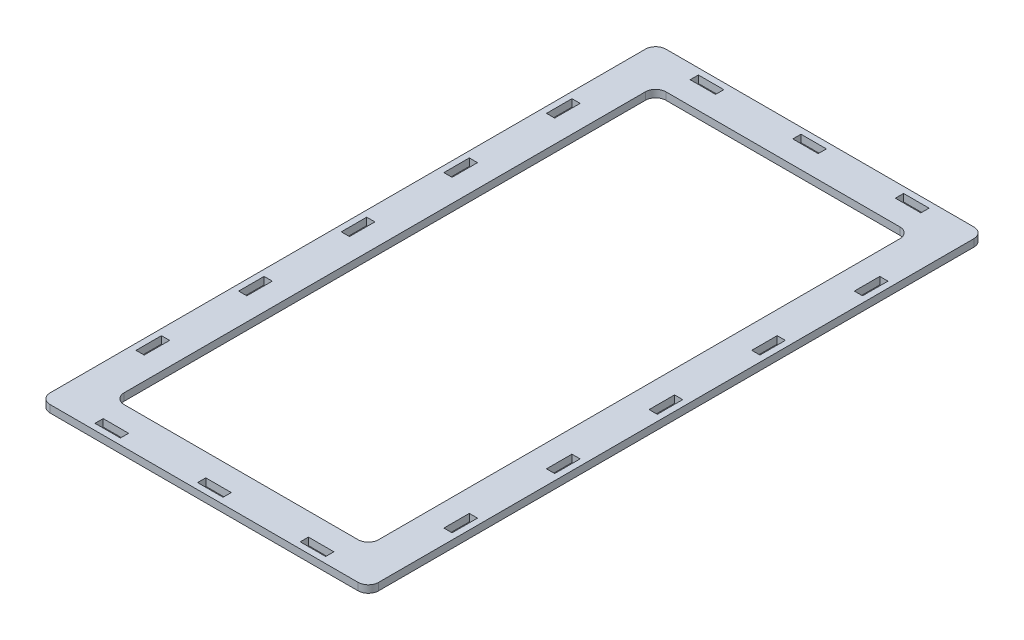
SolidWorks part; units mm, degrees
ref_plane "前视基准面" through (0, 0, 0) normal (0, 0, 1) x (1, 0, 0)
ref_plane "上视基准面" through (0, 0, 0) normal (0, 1, 0) x (1, 0, 0)
ref_plane "右视基准面" through (0, 0, 0) normal (1, 0, 0) x (0, 0, -1)
other "Configuration Table"
sketch "草图1" plane through (0, 0, 0) normal (0, 1, 0) x (1, 0, 0)
  line L1 (-400, 750) -> (400, 750)
  line L2 (-400, 750) -> (-400, -750)
  line L3 (-400, -750) -> (400, -750)
  line L4 (400, 750) -> (400, -750)
  line L5 (-385, -469) -> (-365, -469)
  line L6 (-385, -469) -> (-385, -531)
  line L7 (-385, -531) -> (-365, -531)
  line L8 (-365, -469) -> (-365, -531)
  line L9 (-281, -735) -> (-219, -735)
  line L10 (-281, -735) -> (-281, -715)
  line L11 (-281, -715) -> (-219, -715)
  line L12 (-219, -735) -> (-219, -715)
  line L13 (-310, 660) -> (310, 660)
  line L14 (-310, 660) -> (-310, -660)
  line L15 (-310, -660) -> (310, -660)
  line L16 (310, 660) -> (310, -660)
  point P4 (-400, 0)
  point P6 (0, -750)
  point P11 (-385, -500)
  point P20 (0, -660)
  point P21 (-310, 0)
  point P22 (-250, -735)
  point P23 (-219, -725)
  point P24 (-375, -531)
  dimension "D1" = 800
  dimension "D2" = 1500
  dimension "D3" = 250
  dimension "D4" = 20
  dimension "D5" = 62
  dimension "D6" = 90
  dimension "D7" = 90
  dimension "D8" = 62
  dimension "D9" = 20
  dimension "D10" = 119
  dimension "D11" = 25
  dimension "D12" = 25
  dimension "D13" = 150
extrude "凸台-拉伸1" add sketch "草图1" along normal blind 18 contours L2 L3 L4 L1 | L14 L15 L16 L13
extrude "切除-拉伸1" cut sketch "草图1<5>" along normal through all contours L7 L8 L5 L6
sketch "草图1<5>" plane through (0, 0, 0) normal (0, 1, 0) x (1, 0, 0) same geometry as "草图1"
pattern_linear "阵列(线性)1" count 5 spacing 250 along (0, 0, -1) of "切除-拉伸1"
mirror "镜向1" about plane through (0, 0, 0) normal (1, 0, 0) of "切除-拉伸1", "阵列(线性)1"
extrude "切除-拉伸2" cut sketch "草图1<4>" along normal through all contours L12 L11 L10 L9
sketch "草图1<4>" plane through (0, 0, 0) normal (0, 1, 0) x (1, 0, 0) same geometry as "草图1"
pattern_linear "阵列(线性)2" count 3 spacing 250 along (1, 0, 0) of "切除-拉伸2"
mirror "镜向2" about plane through (0, 0, 0) normal (0, 0, 1) of "阵列(线性)2", "切除-拉伸2"
fillet "圆角1" radius 25 4 edges at (-400, 9, -750) (400, 9, -750) (400, 9, 750) (-400, 9, 750)
fillet "圆角2" radius 25 4 edges at (-310, 9, -660) (310, 9, -660) (310, 9, 660) (-310, 9, 660)
